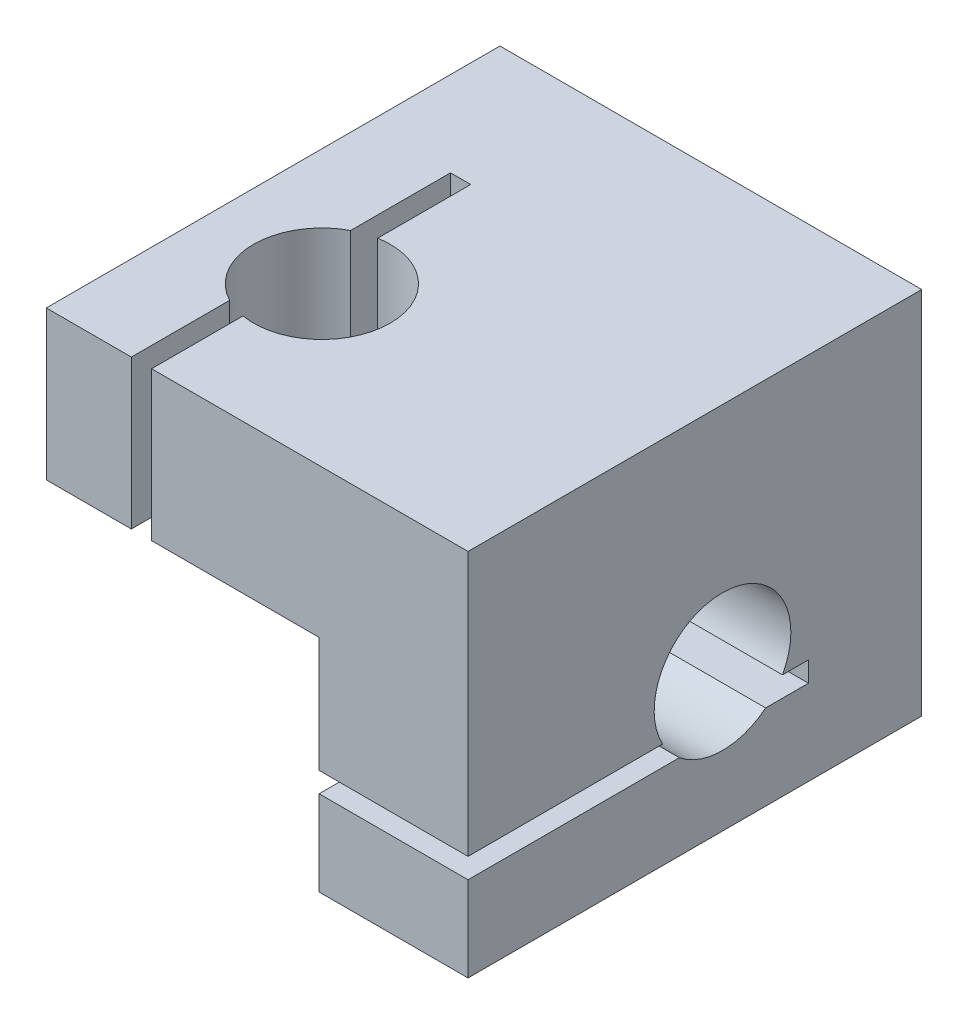
SolidWorks part; units mm, degrees
material "Rubber"
ref_plane "Front Plane" through (0, 0, 0) normal (0, 0, 1) x (1, 0, 0)
ref_plane "Top Plane" through (0, 0, 0) normal (0, 1, 0) x (1, 0, 0)
ref_plane "Right Plane" through (0, 0, 0) normal (1, 0, 0) x (0, 0, -1)
sketch "Sketch1" plane through (0, 0, 0) normal (0, 0, 1) x (1, 0, 0)
  line L1 (0, 0) -> (14, 0)
  line L2 (0, 0) -> (0, -34.73)
  line L3 (0, -34.73) -> (14, -34.73)
  line L4 (14, 0) -> (14, -34.73)
  line L5 (0, 0) -> (-25.65, 0)
  line L6 (0, 0) -> (0, -14)
  line L7 (0, -14) -> (-25.65, -14)
  line L8 (-25.65, 0) -> (-25.65, -14)
  dimension "D1" = 14
  dimension "D2" = 39.65
  dimension "D3" = 34.73
extrude "Boss-Extrude1" add sketch "Sketch1" along normal blind 42.65 contours L5 L8 L7 L2 | L4 L1 L2 L3 region at (7, -17.365, 0) region at (-12.825, -7, 0)
sketch "Sketch2" plane through (0, -14, 0) normal (0, -1, 0) x (1, 0, 0)
  line L0 (-25.65, 42.65) -> (-25.65, 0) construction
  line L1 (0, 42.65) -> (-25.65, 42.65) construction
  circle A0 centre (-14.665, 27.725) radius 6.425
  point P2 (-21.09, 27.725)
  point P6 (-14.665, 34.15)
  dimension "D1" = 12.85
  dimension "D2" = 4.56
  dimension "D3" = 8.5
extrude "Cut-Extrude1" cut sketch "Sketch2" against normal blind 42.65
sketch "Sketch3" plane through (0, -14, 0) normal (0, -1, 0) x (1, 0, 0)
  line L0 (0, 42.65) -> (-25.65, 42.65) construction
  line L1 (-17.65, 42.65) -> (-15.75, 42.65)
  line L2 (-17.65, 42.65) -> (-17.65, 12.65)
  line L3 (-17.65, 12.65) -> (-15.75, 12.65)
  line L4 (-15.75, 42.65) -> (-15.75, 12.65)
  line L5 (-25.65, 42.65) -> (-25.65, 0) construction
  dimension "D1" = 8
  dimension "D2" = 1.9
  dimension "D3" = 30
extrude "Cut-Extrude2" cut sketch "Sketch3" against normal blind 42.65
sketch "Sketch4" plane through (0, 0, 0) normal (-1, 0, 0) x (0, 0, 1)
  line L0 (42.65, -34.73) -> (0, -34.73) construction
  line L1 (42.65, -14) -> (42.65, -34.73) construction
  circle A0 centre (18.725, -21.745) radius 6.425
  point P2 (25.15, -21.745)
  point P3 (18.725, -28.17)
  dimension "D1" = 12.85
  dimension "D2" = 6.56
  dimension "D3" = 17.5
extrude "Cut-Extrude3" cut sketch "Sketch4" against normal blind 42.65
sketch "Sketch5" plane through (0, 0, 0) normal (-1, 0, 0) x (0, 0, 1)
  line L0 (42.65, -14) -> (42.65, -34.73) construction
  line L1 (42.65, -26.73) -> (10.65, -26.73)
  line L2 (42.65, -26.73) -> (42.65, -24.83)
  line L3 (42.65, -24.83) -> (10.65, -24.83)
  line L4 (10.65, -26.73) -> (10.65, -24.83)
  line L5 (42.65, -34.73) -> (0, -34.73) construction
  dimension "D1" = 8
  dimension "D2" = 1.9
  dimension "D3" = 32
extrude "Cut-Extrude4" cut sketch "Sketch5" against normal blind 42.65
hole_wizard "M3x0.5 Tapped Hole1" positions "Sketch6" profile "Sketch8" tap size "M3x0.5" standard "ANSI Metric"
sketch "Sketch6" plane through (0, 0, 0) normal (0, 0, -1) x (-1, 0, 0)
  line L0 (-14, 0) -> (25.65, 0) construction
  line L1 (25.65, 0) -> (25.65, -14) construction
  line L2 (-14, 0) -> (-14, -34.73) construction
  point P0 (1.1, -5.25)
  point P2 (13.5, -5.25)
  point P4 (-6.99, -21.8)
  dimension "D1" = 12.4
  dimension "D2" = 5.25
  dimension "D3" = 12.15
  dimension "D4" = 7.01
  dimension "D5" = 21.8
cosmetic thread "Hole Thread1" parameters "D1"=42.38, "D2"=3
cosmetic thread "Hole Thread2" parameters "D1"=42.38, "D2"=3
cosmetic thread "Hole Thread3" parameters "D1"=42.38, "D2"=3
sketch "Sketch8" plane through (-1.1, -5.25, 0) normal (1, 0, 0) x (0, 1, 0)
  line L0 (0, 0) -> (0, 10.7511)
  line L1 (0, 10.7511) -> (1.25, 10)
  line L2 (1.25, 10) -> (1.25, 0.275)
  line L3 (1.25, 0.275) -> (1.525, 0)
  line L5 (1.525, 0) -> (0, 0)
  line L6 (-1.25, 0.275) -> (-1.525, 0) construction
  line L10 (0, 10.7511) -> (-1.25, 10) construction
  line L11 (0, -6.35) -> (0, 107.95) construction
  dimension "Tap Drill Dia." = 2.5
  dimension "Tap Drill Depth" = 10
  dimension "Near C'Sink Dia." = 3.05
  dimension "Near C'Sink Angle" = 90
  dimension "Drill Angle" = 118
ref_axis "Axis1" through (-14.665, 0.9766, 27.725) along (0, -1, 0)
ref_point "Point1"
ref_plane "Plane2" through (-14.665, 0, 0) normal (-1, 0, 0) x (0, 0, 1)
ref_point "Point2"
ref_plane "Plane3" through (0, 0, 18.725) normal (0, 0, -1) x (-1, 0, 0)
